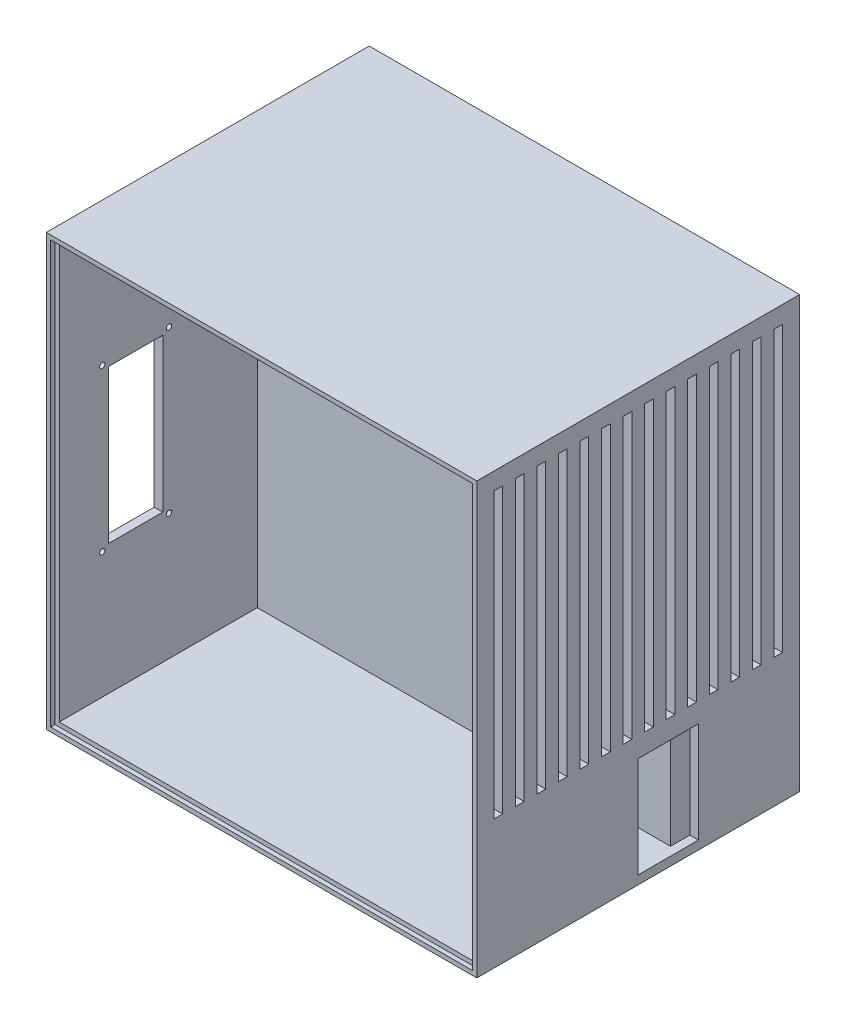
SolidWorks part; units mm, degrees
ref_plane "Front Plane" through (0, 0, 0) normal (0, 0, 1) x (1, 0, 0)
ref_plane "Top Plane" through (0, 0, 0) normal (0, 1, 0) x (1, 0, 0)
ref_plane "Right Plane" through (0, 0, 0) normal (1, 0, 0) x (0, 0, -1)
sketch "Sketch4" plane through (0, 0, 0) normal (0, 0, 1) x (1, 0, 0)
  line L1 (0, 0) -> (200, 0)
  line L2 (0, 0) -> (0, 200)
  line L3 (0, 200) -> (200, 200)
  line L4 (200, 0) -> (200, 200)
  dimension "D1" = 200
  dimension "D2" = 200
extrude "Boss-Extrude1" add sketch "Sketch4" along normal blind 150 contours L2 L1 L4 L3
sketch "Sketch5" plane through (0, 0, 150) normal (0, 0, 1) x (1, 0, 0)
  line L0 (100, 0) -> (100, 2) construction
  line L1 (0, 0) -> (200, 0) construction
  line L2 (0, 100) -> (2, 100) construction
  line L6 (200, 100) -> (198, 100) construction
  line L7 (200, 0) -> (200, 200) construction
  line L8 (100, 200) -> (100, 198) construction
  line L9 (0, 200) -> (200, 200) construction
  line L10 (100, 198) -> (198, 198) construction
  line L11 (198, 198) -> (198, 100) construction
  line L12 (0, 0) -> (0, 200) construction
  line L13 (2, 100) -> (198, 100)
  point P11 (0, 100)
  point P14 (0, 100)
  dimension "D1" = 2
  dimension "D2" = 2
  dimension "D3" = 2
sketch "Sketch6" plane through (0, 0, 150) normal (0, 0, 1) x (1, 0, 0)
  line L0 (2, 100) -> (198, 100) construction
  line L1 (2, 2) -> (198, 2)
  line L2 (2, 2) -> (2, 198)
  line L3 (2, 198) -> (198, 198)
  line L4 (198, 2) -> (198, 198)
  line L5 (2, 2) -> (198, 198) construction
  line L6 (2, 198) -> (198, 2) construction
  point P0 (100, 100)
extrude "Cut-Extrude1" cut sketch "Sketch6" against normal blind 2 contours L2 L1 L4 L3
sketch "Sketch7" plane through (0, 0, 148) normal (0, 0, 1) x (1, 0, 0)
  line L0 (100, 198) -> (100, 196) construction
  line L1 (2, 100) -> (4, 100) construction
  line L2 (2, 100) -> (198, 100) construction
  line L3 (198, 100) -> (196, 100) construction
  line L4 (100, 2) -> (100, 4) construction
  line L6 (4, 4) -> (196, 4)
  line L7 (4, 4) -> (4, 196)
  line L8 (4, 196) -> (196, 196)
  line L9 (196, 4) -> (196, 196)
  line L10 (4, 4) -> (196, 196) construction
  line L11 (4, 196) -> (196, 4) construction
  point P14 (100, 100)
  dimension "D1" = 2
  dimension "D2" = 2
  dimension "D3" = 2
extrude "Cut-Extrude2" cut sketch "Sketch7" against normal blind 92
sketch "Sketch9" plane through (200, 0, 0) normal (1, 0, 0) x (0, 0, -1)
  line L0 (-150, 100) -> (0, 100) construction
  line L1 (-150, 0) -> (-150, 200) construction
  line L2 (0, 0) -> (0, 200) construction
  line L3 (-75, 200) -> (-75, 0) construction
  line L4 (-150, 0) -> (0, 0) construction
  line L5 (0, 0) -> (0, 4) construction
  line L6 (0, 0) -> (-4, 0) construction
  line L7 (-4, 0) -> (-4, 4) construction
  line L8 (-4, 4) -> (0, 4) construction
  line L9 (-4, 4) -> (-150, 4) construction
  line L10 (-75, 0) -> (-75, 4) construction
  line L11 (-150, 200) -> (0, 200) construction
  line L12 (-75, 4) -> (-47, 4)
  line L13 (-75, 4) -> (-75, 50.8)
  line L14 (-75, 50.8) -> (-47, 50.8)
  line L15 (-47, 4) -> (-47, 50.8)
  dimension "D1" = 4
  dimension "D2" = 4
  dimension "D3" = 28
  dimension "D4" = 46.8
sketch "Sketch11" plane through (0, 0, 0) normal (-1, 0, 0) x (0, 0, 1)
  line L0 (75, 0) -> (75, 200) construction
  line L2 (150, 0) -> (0, 0) construction
  line L3 (150, 200) -> (0, 200) construction
  line L5 (150, 0) -> (150, 200) construction
  line L6 (75, 0) -> (75, 4) construction
  line L7 (150, 100) -> (146, 100) construction
  line L10 (75, 4) -> (150, 4) construction
  line L11 (146, 100) -> (146, 4) construction
  line L12 (75, 100) -> (150, 100) construction
  line L13 (99.9, 64.4) -> (125.1, 64.4)
  line L14 (99.9, 64.4) -> (99.9, 135.6)
  line L15 (99.9, 135.6) -> (125.1, 135.6)
  line L16 (125.1, 64.4) -> (125.1, 135.6)
  line L17 (99.9, 64.4) -> (125.1, 135.6) construction
  line L18 (99.9, 135.6) -> (125.1, 64.4) construction
  line L19 (94.5, 60) -> (130.5, 60)
  line L20 (94.5, 60) -> (94.5, 140)
  line L21 (94.5, 140) -> (130.5, 140)
  line L22 (130.5, 60) -> (130.5, 140)
  line L23 (94.5, 60) -> (130.5, 140) construction
  line L24 (94.5, 140) -> (130.5, 60) construction
  line L25 (97, 62.5) -> (128, 62.5)
  line L26 (97, 62.5) -> (97, 137.5)
  line L27 (97, 137.5) -> (128, 137.5)
  line L28 (128, 62.5) -> (128, 137.5)
  line L29 (97, 62.5) -> (128, 137.5) construction
  line L30 (97, 137.5) -> (128, 62.5) construction
  circle A0 centre (128, 137.5) radius 1.25
  circle A1 centre (97, 137.5) radius 1.25
  circle A2 centre (97, 62.5) radius 1.25
  circle A3 centre (128, 62.5) radius 1.25
  point P8 (112.5, 100)
  point P19 (112.5, 100)
  point P24 (112.5, 100)
  dimension "D1" = 4
  dimension "D2" = 4
  dimension "D9" = 2.5
  dimension "D10" = 2.5
  dimension "D11" = 2.5
  dimension "D12" = 2.5
  dimension "D3" = 25.2
  dimension "D4" = 71.2
  dimension "D5" = 36
  dimension "D6" = 80
  dimension "D7" = 75
  dimension "D8" = 31
sketch "Sketch12" plane through (0, 0, 0) normal (-1, 0, 0) x (0, 0, 1)
  line L0 (75, 200) -> (75, 0) construction
  line L1 (150, 200) -> (0, 200) construction
  line L2 (150, 0) -> (0, 0) construction
  line L3 (75, 100) -> (0, 100) construction
  line L4 (150, 0) -> (150, 200) construction
  line L5 (0, 0) -> (0, 200) construction
  line L6 (0, 200) -> (4, 200) construction
  line L7 (0, 200) -> (0, 196) construction
  line L8 (4, 200) -> (4, 0) construction
  line L9 (0, 196) -> (150, 196) construction
  line L10 (37.5, 100) -> (37.5, 196) construction
  line L11 (37.5, 100) -> (37.5, 0) construction
  circle A0 centre (37.5, 100) radius 0.55
  circle A1 centre (37.5, 80) radius 0.55
  circle A2 centre (37.5, 60) radius 0.55
  circle A3 centre (37.5, 148) radius 1
  dimension "D1" = 4
  dimension "D2" = 4
  dimension "D3" = 1.1
  dimension "D5" = 2
sketch "Sketch13" plane through (200, 0, 0) normal (1, 0, 0) x (0, 0, -1)
  line L0 (-4, 4) -> (-4, 200) construction
  line L1 (-150, 200) -> (0, 200) construction
  line L2 (-75, 200) -> (-75, 196) construction
  line L3 (-75, 200) -> (-75, 0) construction
  line L4 (-150, 100) -> (-146, 100) construction
  line L5 (-150, 100) -> (0, 100) construction
  line L6 (-4, 196) -> (-146, 196) construction
  line L7 (-146, 196) -> (-146, 4) construction
  line L8 (-4, 4) -> (-150, 4) construction
  line L9 (-4, 196) -> (-4, 192) construction
  line L10 (-4, 196) -> (-8, 196) construction
  line L11 (-8, 196) -> (-8, 192) construction
  line L12 (-8, 192) -> (-4, 192) construction
  line L13 (-75, 100) -> (-75, 60) construction
  line L14 (-75, 60) -> (-4, 60) construction
  line L15 (-146, 196) -> (-142, 196) construction
  line L16 (-8, 192) -> (-12, 192)
  line L17 (-8, 192) -> (-8, 60)
  line L18 (-8, 60) -> (-12, 60)
  line L19 (-12, 192) -> (-12, 60)
  line L20 (-146, 196) -> (-146, 192) construction
  line L21 (-142, 196) -> (-142, 192) construction
  line L22 (-142, 192) -> (-146, 192) construction
  line L23 (-18, 192) -> (-18, 60)
  line L24 (-18, 192) -> (-22, 192)
  line L25 (-22, 192) -> (-22, 60)
  line L26 (-18, 60) -> (-22, 60)
  line L27 (-28, 192) -> (-28, 60)
  line L28 (-28, 192) -> (-32, 192)
  line L29 (-32, 192) -> (-32, 60)
  line L30 (-28, 60) -> (-32, 60)
  line L31 (-38, 192) -> (-38, 60)
  line L32 (-38, 192) -> (-42, 192)
  line L33 (-42, 192) -> (-42, 60)
  line L34 (-38, 60) -> (-42, 60)
  line L35 (-48, 192) -> (-48, 60)
  line L36 (-48, 192) -> (-52, 192)
  line L37 (-52, 192) -> (-52, 60)
  line L38 (-48, 60) -> (-52, 60)
  line L39 (-58, 192) -> (-58, 60)
  line L40 (-58, 192) -> (-62, 192)
  line L41 (-62, 192) -> (-62, 60)
  line L42 (-58, 60) -> (-62, 60)
  line L43 (-68, 192) -> (-68, 60)
  line L44 (-68, 192) -> (-72, 192)
  line L45 (-72, 192) -> (-72, 60)
  line L46 (-68, 60) -> (-72, 60)
  line L47 (-78, 192) -> (-78, 60)
  line L48 (-78, 192) -> (-82, 192)
  line L49 (-82, 192) -> (-82, 60)
  line L50 (-78, 60) -> (-82, 60)
  line L51 (-88, 192) -> (-88, 60)
  line L52 (-88, 192) -> (-92, 192)
  line L53 (-92, 192) -> (-92, 60)
  line L54 (-88, 60) -> (-92, 60)
  line L55 (-98, 192) -> (-98, 60)
  line L56 (-98, 192) -> (-102, 192)
  line L57 (-102, 192) -> (-102, 60)
  line L58 (-98, 60) -> (-102, 60)
  line L59 (-108, 192) -> (-108, 60)
  line L60 (-108, 192) -> (-112, 192)
  line L61 (-112, 192) -> (-112, 60)
  line L62 (-108, 60) -> (-112, 60)
  line L63 (-118, 192) -> (-118, 60)
  line L64 (-118, 192) -> (-122, 192)
  line L65 (-122, 192) -> (-122, 60)
  line L66 (-118, 60) -> (-122, 60)
  line L67 (-128, 192) -> (-128, 60)
  line L68 (-128, 192) -> (-132, 192)
  line L69 (-132, 192) -> (-132, 60)
  line L70 (-128, 60) -> (-132, 60)
  line L71 (-138, 192) -> (-138, 60)
  line L72 (-138, 192) -> (-142, 192)
  line L73 (-142, 192) -> (-142, 60)
  line L74 (-138, 60) -> (-142, 60)
  dimension "D1" = 4
  dimension "D2" = 4
  dimension "D3" = 4
  dimension "D4" = 4
  dimension "D5" = 40
  dimension "D6" = 4
  dimension "D7" = 4
  dimension "D8" = 14
extrude "Inlet" cut sketch "Sketch9" against normal blind 4 contours L13 L12 L15 L14
extrude "Airflow" cut sketch "Sketch13" against normal blind 4
extrude "Cut-Extrude5" cut sketch "Sketch11" against normal blind 4 contours L14 L13 L16 L15
extrude "LCD/Mounting" cut sketch "Sketch11<4>" against normal blind 4 contours A2 | A0 | A1 | A3
sketch "Sketch11<4>" plane through (0, 0, 0) normal (-1, 0, 0) x (0, 0, 1) same geometry as "Sketch11"
extrude "Post/Knob Mounting" cut sketch "Sketch12" against normal blind 4
equation "\"L\"= 100mm"
equation "\"T\"= 1mm"
equation "\"D1@Sketch4\"=2*\"L\""
equation "\"D2@Sketch4\"=2*\"L\""
equation "\"D1@Boss-Extrude1\"=1.5*\"L\""
equation "\"D1@Sketch5\"=(1/50)*\"L\""
equation "\"D2@Sketch5\"=(1/50)*\"L\""
equation "\"D3@Sketch5\"=(1/50)*\"L\""
equation "\"D4@Sketch5\"=(1/50)*\"L\""
equation "\"D1@Cut-Extrude1\"=(1/50)*\"L\""
equation "\"D1@Sketch7\"=(1/50)*\"L\""
equation "\"D2@Sketch7\"=(1/50)*\"L\""
equation "\"D3@Sketch7\"=(1/50)*\"L\""
equation "\"D4@Sketch7\"=(1/50)*\"L\""
equation "\"D1@Sketch9\"=4*\"T\""
equation "\"D2@Sketch9\"=4*\"T\""
equation "\"D3@Sketch9\"=(7/25)*\"L\""
equation "\"D4@Sketch9\"=(46.8/100)*\"L\""
equation "\"D1@Sketch11\"=4*\"T\""
equation "\"D2@Sketch11\"=4*\"T\""
equation "\"D3@Sketch11\"=(25.2/100)*\"L\""
equation "\"D4@Sketch11\"=(71.2/100)*\"L\""
equation "\"D5@Sketch11\"=(9/25)*\"L\""
equation "\"D6@Sketch11\"=(4/5)*\"L\""
equation "\"D7@Sketch11\"=(3/4)*\"L\""
equation "\"D8@Sketch11\"=(31/100)*\"L\""
equation "\"D9@Sketch11\"=(1/40)*\"L\""
equation "\"D10@Sketch11\"=(1/40)*\"L\""
equation "\"D11@Sketch11\"=(1/40)*\"L\""
equation "\"D12@Sketch11\"=(1/40)*\"L\""
equation "\"D1@Sketch12\"=4*\"T\""
equation "\"D2@Sketch12\"=4*\"T\""
equation "\"D3@Sketch12\"=(1.1/100)*\"L\""
equation "\"D5@Sketch12\"=(1/50)*\"L\""
equation "\"D1@Sketch13\"=4*\"T\""
equation "\"D2@Sketch13\"=4*\"T\""
equation "\"D3@Sketch13\"=4*\"T\""
equation "\"D4@Sketch13\"=4*\"T\""
equation "\"D5@Sketch13\"=(2/5)*\"L\""
equation "\"D6@Sketch13\"=4*\"T\""
equation "\"D7@Sketch13\"=4*\"T\""
